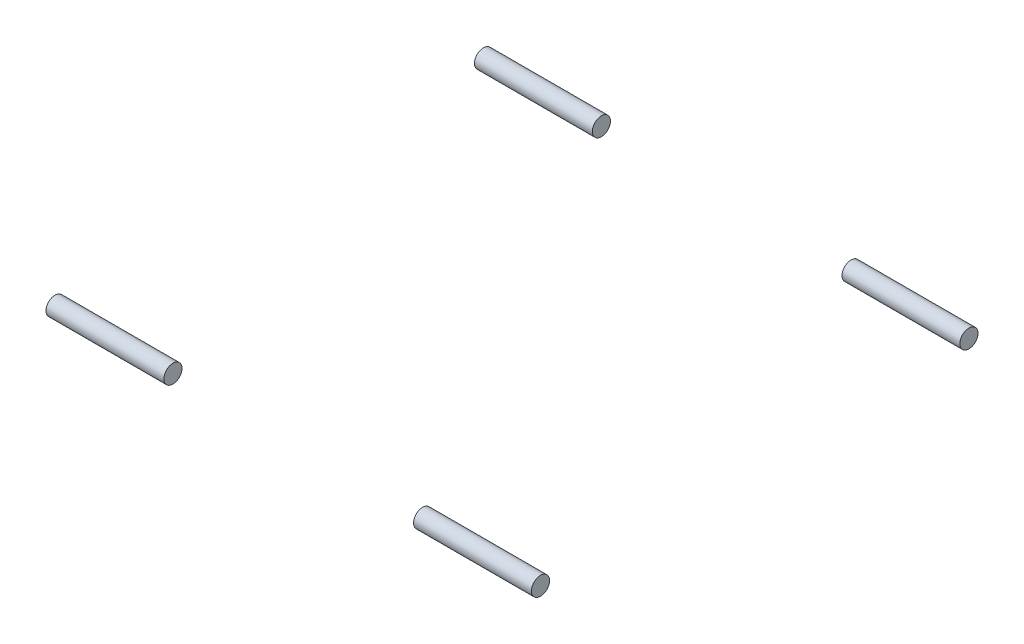
SolidWorks part; units mm, degrees
material "6061-T6 (SS)"
ref_plane "Front Plane" through (0, 0, 0) normal (0, 0, 1) x (1, 0, 0)
ref_plane "Top Plane" through (0, 0, 0) normal (0, 1, 0) x (1, 0, 0)
ref_plane "Right Plane" through (0, 0, 0) normal (1, 0, 0) x (0, 0, -1)
sketch "Sketch1" plane through (84.975, 0, 0) normal (-1, 0, 0) x (0, 0, 1)
  circle A0 centre (150, 0) radius 3.175
  circle A1 centre (0, 0) radius 3.175
  circle A2 centre (0, 0) radius 3.175 construction
  circle A3 centre (150, 0) radius 3.175 construction
extrude "Boss-Extrude1" add sketch "Sketch1" along normal up to surface (41.275 mm away)
mirror "Mirror1" about plane through (0, 0, 0) normal (1, 0, 0) of bodies 101 102
